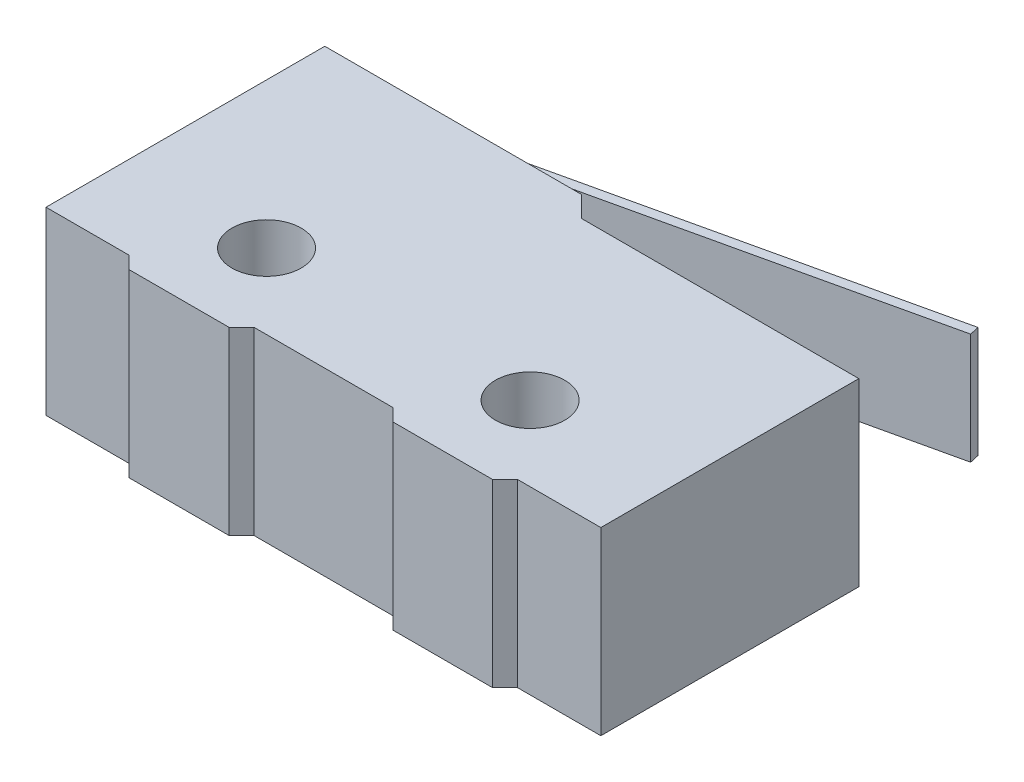
SolidWorks part; units mm, degrees
ref_plane "Front Plane" through (0, 0, 0) normal (0, 0, 1) x (1, 0, 0)
ref_plane "Top Plane" through (0, 0, 0) normal (0, 1, 0) x (1, 0, 0)
ref_plane "Right Plane" through (0, 0, 0) normal (1, 0, 0) x (0, 0, -1)
sketch "스케치1" plane through (0, 0, 0) normal (0, 1, 0) x (1, 0, 0)
  line L1 (-10, 5.25) -> (10, 5.25)
  line L2 (-10, 5.25) -> (-10, -5.25)
  line L3 (-10, -5.25) -> (10, -5.25)
  line L4 (10, 5.25) -> (10, -5.25)
  dimension "D1" = 20
  dimension "D2" = 10.5
  dimension "D3" = 10
  dimension "D4" = 5.25
extrude "보스-돌출1" add sketch "스케치1" along normal blind 6.5
sketch "스케치2" plane through (0, 6.5, 0) normal (0, 1, 0) x (1, 0, 0)
  line L0 (-11.4248, -2.1) -> (49988.5752, -2.1) construction
  line L1 (-4.75, -0.1929) -> (-4.75, -50000.1929) construction
  line L2 (4.75, 1.0289) -> (4.75, -49998.9711) construction
  line L3 (10, -5.25) -> (10, 5.25) construction
  line L4 (-10, 5.25) -> (-10, -5.25) construction
  line L5 (-10, -5.25) -> (10, -5.25) construction
  circle A0 centre (-4.75, -2.1) radius 1.25
  circle A1 centre (4.75, -2.1) radius 1.25
  dimension "D1" = 5.25
  dimension "D2" = 5.25
  dimension "D3" = 3.15
extrude "컷-돌출1" cut sketch "스케치2" against normal blind 6.5
sketch "스케치3" plane through (0, 6.5, 0) normal (0, 1, 0) x (1, 0, 0)
  line L0 (-4.75, -2.1) -> (-4.75, -50002.1) construction
  line L1 (4.75, -2.1) -> (4.75, -50002.1) construction
  line L2 (2.5, -2.5079) -> (2.5, -50002.5079) construction
  line L3 (7, -1.9506) -> (7, -50001.9506) construction
  line L4 (-2.5, -1.9077) -> (-2.5, -50001.9077) construction
  line L6 (-7, -1.8863) -> (-7, -50001.8863) construction
  line L7 (-11.4677, -4.8) -> (49988.5323, -4.8) construction
  line L8 (-10, -5.25) -> (10, -5.25) construction
  line L10 (-11.4463, -4.8) -> (-7, -4.8)
  line L11 (-11.4463, -4.8) -> (-11.4463, -5.8089)
  line L12 (-11.4463, -5.8089) -> (-7, -5.8089)
  line L13 (-7, -4.8) -> (-7, -5.8089)
  line L14 (-2.5, -5.8089) -> (2.5, -5.8089)
  line L15 (-2.5, -5.8089) -> (-2.5, -4.8)
  line L16 (-2.5, -4.8) -> (2.5, -4.8)
  line L17 (2.5, -5.8089) -> (2.5, -4.8)
  line L18 (7, -5.8089) -> (10.6532, -5.8089)
  line L19 (7, -5.8089) -> (7, -4.8)
  line L20 (7, -4.8) -> (10.6532, -4.8)
  line L21 (10.6532, -5.8089) -> (10.6532, -4.8)
  dimension "D1" = 0.45
  dimension "D2" = 4.5
  dimension "D3" = 4.5
  dimension "D4" = 2.25
  dimension "D5" = 2.25
extrude "컷-돌출2" cut sketch "스케치3" against normal blind 6.5
chamfer "모따기1" distance 0.45 angle 45 4 edges at (7, 3.25, 5.25) (2.5, 3.25, 5.25) (-2.5, 3.25, 5.25) (-7, 3.25, 5.25)
sketch "스케치4" plane through (0, 6.5, 0) normal (0, 1, 0) x (1, 0, 0)
  line L0 (-10.7603, 4.5) -> (49989.2397, 4.5) construction
  line L1 (0, 6.602) -> (0, -49993.398) construction
  line L2 (10, 5.25) -> (-10, 5.25) construction
  line L3 (-10, 5.25) -> (-10, -4.8) construction
  line L5 (0, 5.5088) -> (10.3102, 5.5088)
  line L6 (0, 5.5088) -> (0, 4.5)
  line L7 (0, 4.5) -> (10.3102, 4.5)
  line L8 (10.3102, 5.5088) -> (10.3102, 4.5)
  dimension "D1" = 0.75
  dimension "D2" = 10
extrude "컷-돌출3" cut sketch "스케치4" against normal blind 6.5
chamfer "모따기2" distance 0.75 angle 45 1 edges at (0, 3.25, -5.25)
ref_plane "평면1" through (0, 5.25, 0) normal (0, 1, 0) x (1, 0, 0)
sketch "스케치5" plane through (0, 5.25, 0) normal (0, 1, 0) x (1, 0, 0)
  line L0 (-7, 4.1993) -> (-7, -49995.8007) construction
  line L1 (-6.9854, 9.5) -> (49993.0146, 9.5) construction
  line L2 (-8.9496, 5.75) -> (49991.0504, 5.75) construction
  line L3 (9.3, 10.1932) -> (9.3, -49989.8068) construction
  line L4 (10, -4.8) -> (10, 4.5) construction
  line L5 (-10, 5.25) -> (-10, -4.8) construction
  line L6 (-0.75, 5.25) -> (-10, 5.25) construction
  line L7 (0, 4.5) -> (10, 4.5) construction
  line L8 (-6.9994, 5.8074) -> (48760.1166, 11040.6792) construction
  line L9 (-5.1353, 6.6981) -> (49994.8647, 6.6981) construction
  line L10 (-13.9851, 4.2268) -> (-4.4166, 6.3919) construction
  line L11 (-14.7305, 3.6992) -> (48752.3855, 11038.571) construction
  line L12 (-6.65, 7.2749) -> (-6.65, 4.6315) construction
  line L13 (-6.65, 5.25) -> (-7, 5.25)
  line L14 (-7, 5.25) -> (-7, 5.8073)
  line L15 (-7, 5.8073) -> (9.3, 9.4956)
  line L16 (9.3, 9.4956) -> (9.3772, 9.1543)
  line L17 (9.3772, 9.1543) -> (-6.65, 5.5277)
  line L18 (-6.65, 5.5277) -> (-6.65, 5.25)
  dimension "D1" = 0.7
  dimension "D2" = 3
  dimension "D3" = 0.5
  dimension "D4" = 5
  dimension "D5" = 0.35
  dimension "D6" = 0.35
extrude "보스-돌출2" add sketch "스케치5" against normal blind 4
